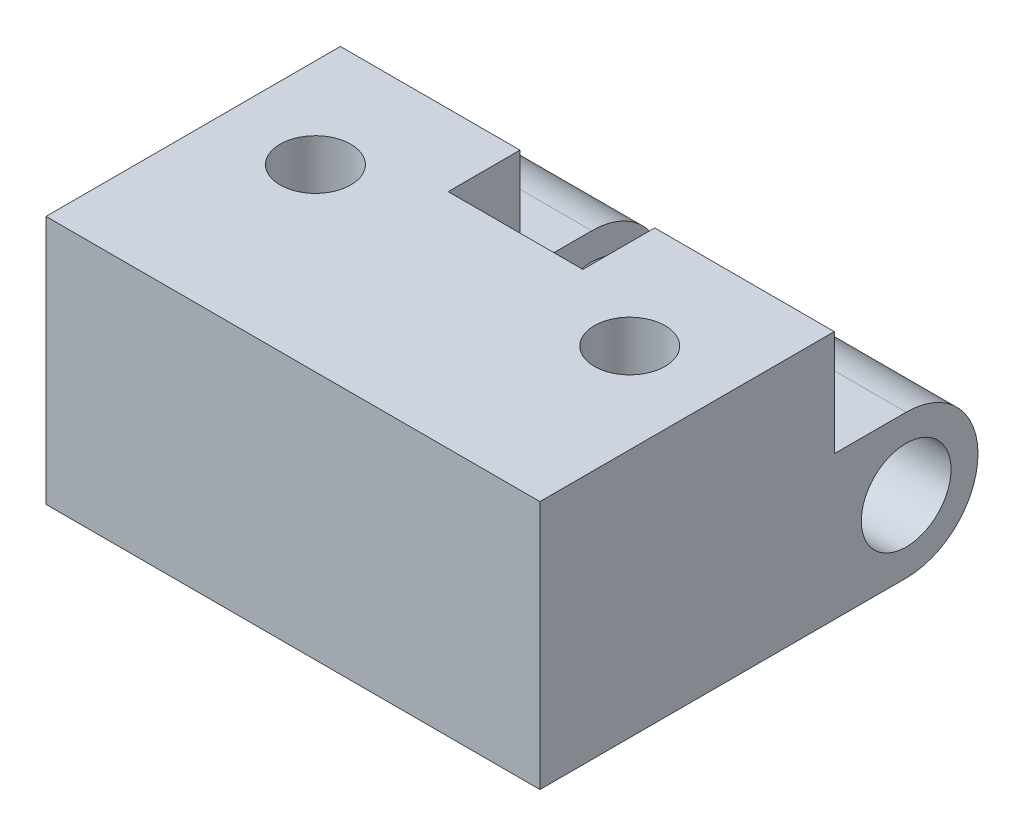
SolidWorks part; units mm, degrees
ref_plane "Front" through (0, 0, 0) normal (0, 0, 1) x (1, 0, 0)
ref_plane "Top" through (0, 0, 0) normal (0, 1, 0) x (1, 0, 0)
ref_plane "Right" through (0, 0, 0) normal (1, 0, 0) x (0, 0, -1)
sketch "Sketch2" plane through (0, 0, 0) normal (1, 0, 0) x (0, 0, -1)
  line L0 (0, 5.08) -> (0, 0)
  line L1 (0, 0) -> (13.1956, 0)
  line L2 (0, 0) -> (0, 5.08)
  line L3 (0, 5.08) -> (13.1956, 5.08)
  line L4 (13.1956, 0) -> (13.1956, 5.08)
  line L5 (0, 5.08) -> (-6.35, 5.08)
  line L6 (0, 0) -> (-6.35, 0)
  line L7 (-6.35, 5.08) -> (-6.35, 0)
  circle A0 centre (6.5978, 2.54) radius 1.5875
  arc A1 (6.5978, 5.08) -> (6.5978, 0) centre (6.5978, 2.54) cw
  point P7 (6.5978, 5.08)
  point P8 (6.5978, 0)
  dimension "D1" = 5.08
  dimension "D2" = 6.35
extrude "Boss-Extrude1" add sketch "Sketch2" along normal blind 6.35 contours L5 L7 L6 L0 | A1 L3 L0 L1 A0 region at (0, 2.54, -3.8093) region at (0, 2.54, 3.175)
sketch "Sketch3" plane through (0, 5.08, 0) normal (0, 1, 0) x (1, 0, 0)
  line L0 (3.175, -6.35) -> (3.175, 0)
  line L1 (6.35, -6.35) -> (0, -6.35) construction
  circle A0 centre (3.175, 0) radius 1.5
  dimension "D1" = 6.35
extrude "Cut-Extrude1" cut sketch "Sketch3" against normal blind 10 contours A0 region at (4.2057, 5.08, 1.0307)
sketch "Sketch4" plane through (6.35, 0, 0) normal (1, 0, 0) x (0, 0, -1)
  line L0 (6.5978, 2.54) -> (2.6291, 2.54)
  line L1 (6.5978, 2.54) -> (1.5178, 2.54)
  line L2 (6.5978, 0) -> (-6.35, 0) construction
  line L3 (1.5178, 0) -> (-6.35, 0)
  line L4 (1.5178, 0) -> (1.5178, 5.08)
  line L5 (1.5178, 5.08) -> (-6.35, 5.08)
  line L6 (-6.35, 0) -> (-6.35, 5.08)
  line M2 (6.5978, 5.08) -> (-6.35, 5.08)
  line M3 (-6.35, 5.08) -> (-6.35, 0)
  line M4 (-6.35, 0) -> (6.5978, 0)
  dimension "D1" = 3.9688
  dimension "D2" = 5.08
extrude "Boss-Extrude2" add sketch "Sketch4" along normal blind 4.7625 contours L4 M4 M2 M3 region at (6.35, 2.54, 2.4161)
ref_plane "Plane1" through (8.7313, 0, 0) normal (1, 0, 0) x (0, 0, -1)
mirror "Mirror1" about plane through (8.7313, 0, 0) normal (1, 0, 0) of "Cut-Extrude1", "Boss-Extrude1"
sketch "Sketch6" plane through (0, 5.08, 0) normal (0, 1, 0) x (1, 0, 0)
  line L0 (6.35, 4.0578) -> (0, 4.0578)
  line L1 (6.35, 6.5978) -> (6.35, 1.5178) construction
  line L2 (0, 6.5978) -> (0, -6.35) construction
  line L3 (0, 4.0578) -> (0, -6.35)
  line L4 (0, -6.35) -> (17.4625, -6.35)
  line L5 (17.4625, -6.35) -> (17.4625, 4.0578)
  line L6 (17.4625, 6.5978) -> (17.4625, -6.35) construction
  line L7 (17.4625, 4.0578) -> (11.1125, 4.0578)
  line L8 (11.1125, 6.5978) -> (11.1125, 1.5178) construction
  line L9 (11.1125, 4.0578) -> (11.1125, 1.5178)
  line L10 (11.1125, 1.5178) -> (6.35, 1.5178)
  line L11 (6.35, 1.5178) -> (6.35, 4.0578)
extrude "Boss-Extrude3" add sketch "Sketch6" along normal blind 3.7375
sketch "Sketch7" plane through (0, 5.08, 0) normal (0, -1, 0) x (1, 0, 0)
  circle A0 centre (14.2875, 0) radius 1.25
  circle A1 centre (3.175, 0) radius 1.25
extrude "Cut-Extrude2" cut sketch "Sketch7" against normal through all
